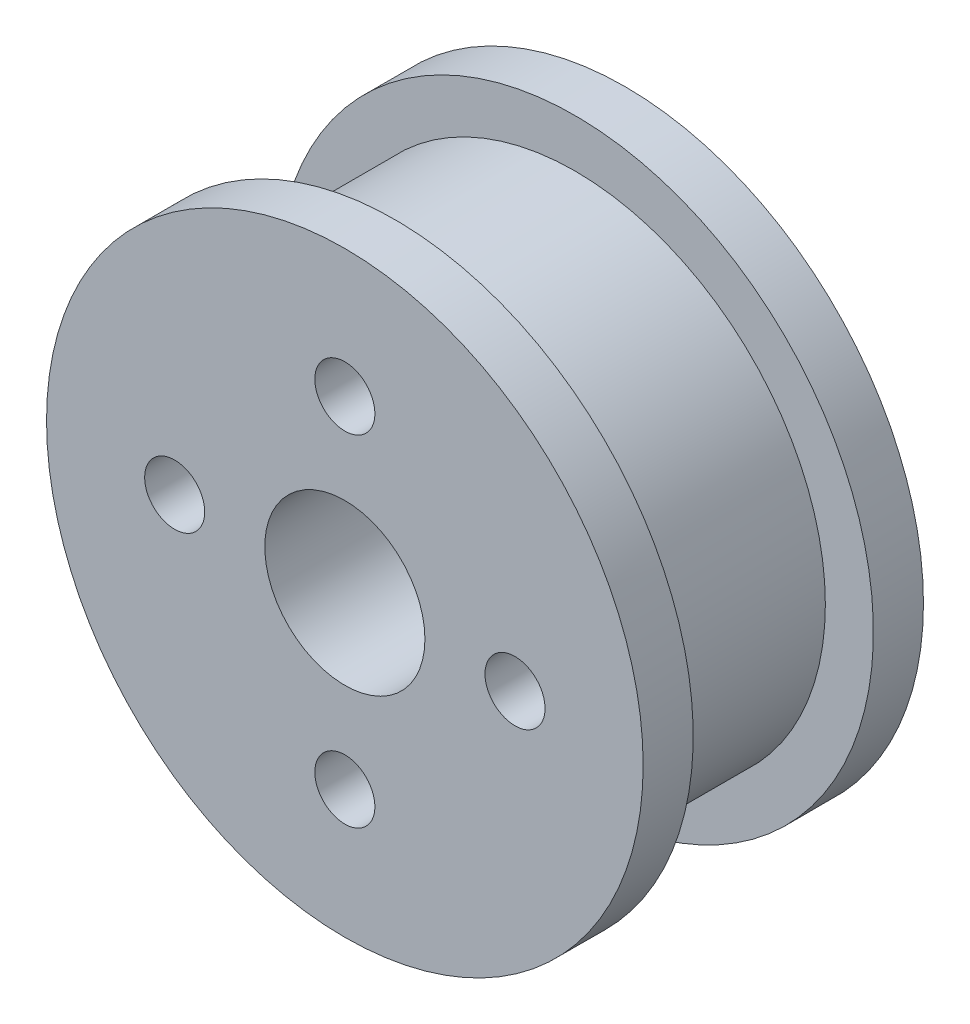
SolidWorks part; units mm, degrees
ref_plane "Front Plane" through (0, 0, 0) normal (0, 0, 1) x (1, 0, 0)
ref_plane "Top Plane" through (0, 0, 0) normal (0, 1, 0) x (1, 0, 0)
ref_plane "Right Plane" through (0, 0, 0) normal (1, 0, 0) x (0, 0, -1)
sketch "Sketch1" plane through (0, 0, 0) normal (0, 0, 1) x (1, 0, 0)
  circle A0 centre (0, 0) radius 14.9
  circle A1 centre (0, 0) radius 4
  dimension "D1" = 29.8
  dimension "D2" = 8
extrude "Boss-Extrude1" add sketch "Sketch1" along normal blind 14
ref_plane "Plane1" through (0, 0, 2.5) normal (0, 0, -1) x (-1, 0, 0)
sketch "Sketch2" plane through (0, 0, 2.5) normal (0, 0, -1) x (-1, 0, 0)
  circle A0 centre (0, 0) radius 12.5
  circle A1 centre (0, 0) radius 14.9
  dimension "D1" = 25
extrude "Cut-Extrude1" cut sketch "Sketch2" against normal blind 9
sketch "Sketch3" plane through (0, 0, 0) normal (0, 0, -1) x (-1, 0, 0)
  circle A1 centre (0, 0) radius 4.5 construction
  circle A2 centre (0, 0) radius 12.5 construction
  circle A3 centre (0, 0) radius 14.9 construction
  circle A4 centre (0, 0) radius 8.5
  circle A5 centre (0, 8.5) radius 1.5
  circle A6 centre (8.5, 0) radius 1.5
  circle A7 centre (0, -8.5) radius 1.5
  circle A8 centre (-8.5, 0) radius 1.5
  dimension "D1" = 9
  dimension "D2" = 2.4
  dimension "D3" = 17
  dimension "D4" = 3
  dimension "D5" = 3
  dimension "D6" = 3
  dimension "D7" = 3
extrude "Cut-Extrude2" cut sketch "Sketch3" against normal through all contours A4 A5 | A4 A5 | A4 A8 | A4 A8 | A4 A6 | A4 A6 | A4 A7 | A4 A7 region at (-7.8401, 0, 0) region at (-9.1122, 0, 0) region at (0, 7.8401, 0) region at (0, 9.1122, 0) region at (0, -9.1122, 0) region at (0, -7.8401, 0) region at (7.8401, 0, 0) region at (9.1122, 0, 0)
